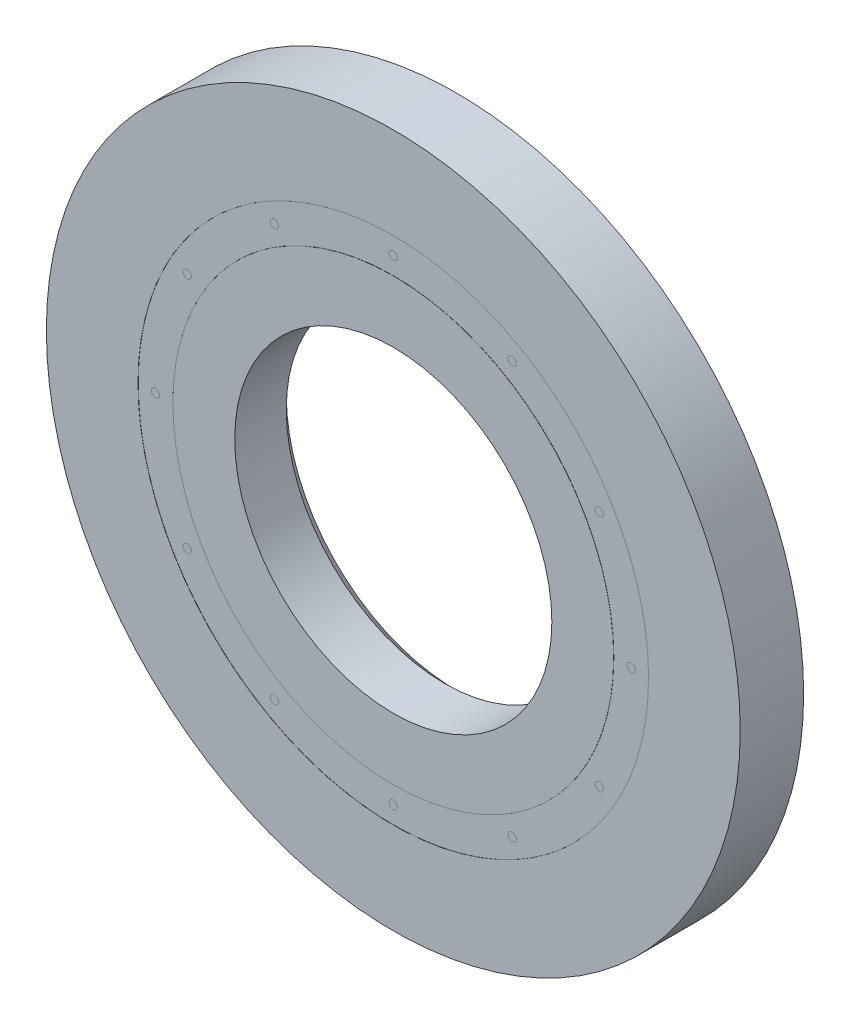
SolidWorks part; units mm, degrees
ref_plane "Front Plane" through (0, 0, 0) normal (0, 0, 1) x (1, 0, 0)
ref_plane "Top Plane" through (0, 0, 0) normal (0, 1, 0) x (1, 0, 0)
ref_plane "Right Plane" through (0, 0, 0) normal (1, 0, 0) x (0, 0, -1)
sketch "Sketch1" plane through (0, 0, 0) normal (1, 0, 0) x (0, 0, -1)
  line L0 (-2.3813, 0) -> (2.3813, 0) construction
  line L1 (0, 6.35) -> (0, -6.35) construction
  line L2 (2.1431, 6.35) -> (-2.1431, 6.35)
  line L3 (-2.1431, 6.35) -> (-2.3813, 6.1119)
  line L4 (-2.3813, 6.1119) -> (-2.3813, 5.1114)
  line L5 (-2.3813, 5.1114) -> (-1.0583, 5.1114)
  line L6 (2.3813, 5.1114) -> (1.0583, 5.1114)
  line L7 (2.3813, 6.1119) -> (2.3813, 5.1114)
  line L8 (2.1431, 6.35) -> (2.3813, 6.1119)
  line L9 (0, 6.35) -> (0, 4.7625) construction
  line L10 (0, 4.7625) -> (0, 3.175) construction
  arc A0 (-1.0583, 5.1114) -> (1.0583, 5.1114) centre (0, 4.7625) cw
  point P14 (0, 3.175)
  dimension "Width" = 4.7625
  dimension "OD" = 12.7
  dimension "D1" = 45
  dimension "D2" = 0.2381
  dimension "Shaft Dia" = 6.35
  dimension "D3" = 2.1167
  dimension "D4" = 0.3489
revolve "Revolve1" add sketch "Sketch1" angle 360 about L0
sketch "Sketch3" plane through (0, 0, 0) normal (1, 0, 0) x (0, 0, -1)
  line L0 (-2.3813, 4.4136) -> (-1.0583, 4.4136)
  line L1 (0, 6.35) -> (0, -6.35) construction
  line L2 (-2.3813, 6.1119) -> (-2.3813, 5.1114) construction
  line L3 (-2.3813, 4.4136) -> (-2.3813, 3.4131)
  line L4 (-2.1431, 6.35) -> (-2.3813, 6.1119) construction
  line L5 (-2.3813, 3.4131) -> (-2.1431, 3.175)
  line L6 (-2.1431, 3.175) -> (2.1431, 3.175)
  line L7 (2.1431, 6.35) -> (2.1431, -6.35) construction
  line L8 (2.1431, 3.175) -> (2.3813, 3.4131)
  line L9 (2.3813, -6.1119) -> (2.3813, 6.1119) construction
  line L10 (2.3813, 3.4131) -> (2.3813, 4.4136)
  line L11 (2.3813, 4.4136) -> (1.0583, 4.4136)
  line L13 (2.1431, 6.35) -> (2.3813, 6.1119) construction
  arc A0 (1.0583, 5.1114) -> (-1.0583, 5.1114) centre (0, 4.7625) ccw construction
  arc A1 (1.0583, 4.4136) -> (-1.0583, 4.4136) centre (0, 4.7625) cw
revolve "Revolve3" add sketch "Sketch3" angle 360 about L0
sketch "Sketch4" plane through (0, 0, 0) normal (1, 0, 0) x (0, 0, -1)
  line L0 (-1.1144, 4.7625) -> (1.1144, 4.7625)
  arc A2 (-1.1144, 4.7625) -> (1.1144, 4.7625) centre (0, 4.7625) cw
  arc A3 (1.0583, 5.1114) -> (-1.0583, 5.1114) centre (0, 4.7625) ccw construction
revolve "Revolve4" add sketch "Sketch4" angle 360 about L0
ref_axis "Axis1" through (0, 0, -2.3813) along (0, 0, 1)
pattern_circular "CirPattern1" count 12 every 30 about axis through (0, 0, -2.3813) along (0, 0, 1) of bodies 104
sketch "Sketch5" plane through (0, 0, 0) normal (1, 0, 0) x (0, 0, -1)
  line L0 (-2.3813, 5.1114) -> (-1.0583, 5.1114) construction
  line L1 (-2.2622, 5.1114) -> (-1.1144, 5.1114)
  line L2 (-2.2622, 5.1114) -> (-2.2622, 4.4136)
  line L3 (-2.2622, 4.4136) -> (-1.1144, 4.4136)
  line L4 (-1.1144, 5.1114) -> (-1.1144, 4.4136)
  line L5 (-2.3813, 4.4136) -> (-1.0583, 4.4136) construction
  line L6 (2.3813, 5.1114) -> (1.0583, 5.1114) construction
  line L7 (2.2622, 5.1114) -> (1.1144, 5.1114)
  line L8 (2.2622, 5.1114) -> (2.2622, 4.4136)
  line L9 (2.2622, 4.4136) -> (1.1144, 4.4136)
  line L10 (1.1144, 5.1114) -> (1.1144, 4.4136)
  line L11 (2.3813, 4.4136) -> (1.0583, 4.4136) construction
  line L12 (-2.1431, 6.35) -> (-2.3813, 6.1119) construction
  point P18 (-2.2622, 6.2309)
revolve "Revolve5" add sketch "Sketch5" angle 360 about L0
sketch "Sketch6" plane through (0, 0, 0) normal (1, 0, 0) x (0, 0, -1)
  line L0 (2.3813, 0) -> (-2.3813, 0) construction
  line L1 (2.3813, 5.1114) -> (1.1113, 5.1114)
  line L2 (2.3813, 5.1114) -> (2.3813, 6.9469)
  line L3 (2.3813, 6.9469) -> (1.1113, 6.9469)
  line L4 (1.1113, 5.1114) -> (1.1113, 6.9469)
  dimension "Th" = 1.27
  dimension "Flange OD" = 13.8938
revolve "Revolve6" add sketch "Sketch6" angle 360 about L0
extrude "Cut-Extrude1" cut sketch "Sketch7" against normal through all
sketch "Sketch7" plane through (-4.8859, 9.6654, -1.1112) normal (0, 0, -1) x (-0.7071, 0.7071, 0)
  circle A1 centre (-10.2893, -3.3796) radius 6.35
equation "\"D2@Sketch1\" = \"Width@Sketch1\"*.05"
equation "\"D3@Sketch1\" = \"Width@Sketch1\"/2.25"
equation "\"D4@Sketch1\" = (((\"OD@Sketch1\"-\"Width@Sketch1\")/2)/3.25)/3.5"
equation "\"D2@CirPattern1\" = 360/\"Balls@CirPattern1\""
